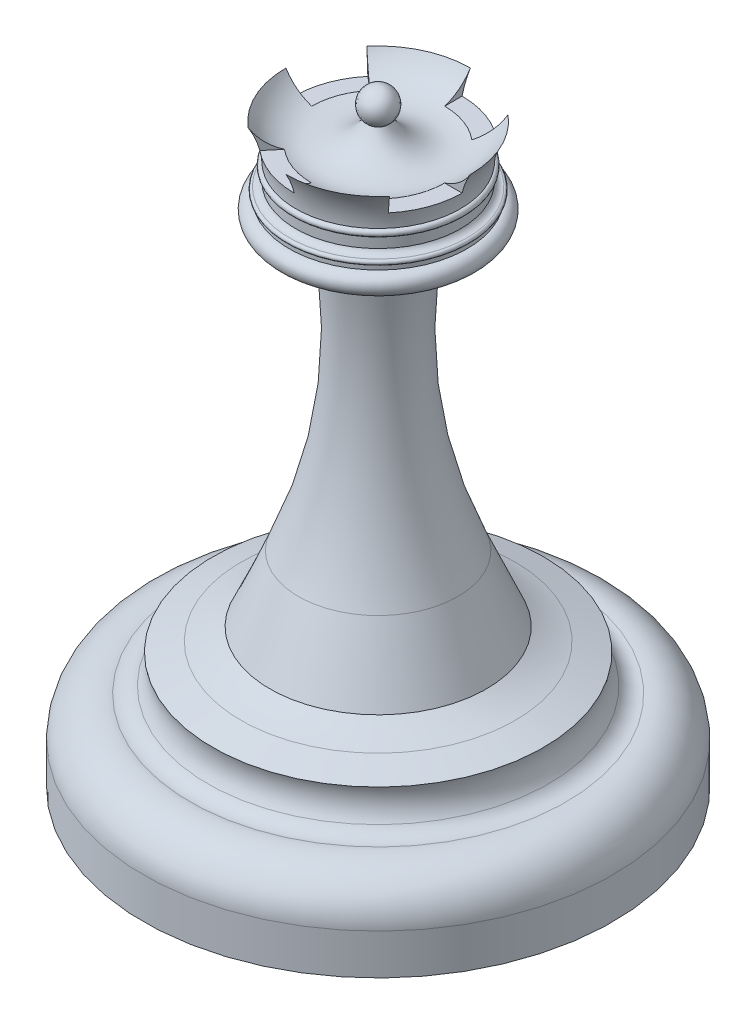
SolidWorks part; units mm, degrees
material "PVC Rigid"
ref_plane "Front Plane" through (0, 0, 0) normal (0, 0, 1) x (1, 0, 0)
ref_plane "Top Plane" through (0, 0, 0) normal (0, 1, 0) x (1, 0, 0)
ref_plane "Right Plane" through (0, 0, 0) normal (1, 0, 0) x (0, 0, -1)
sketch "Sketch1" plane through (0, 0, 0) normal (0, 0, 1) x (1, 0, 0)
  line L0 (0, 0) -> (-11.6, 0)
  line L3 (-11.5941, 2) -> (-11.6, 0)
  line L11 (0, 0) -> (0, 36.8797) construction
  line L18 (-8.1731, 5.7487) -> (-6.7792, 6.2131)
  line L19 (-5.3519, 6.8465) -> (-3.9421, 10.0987)
  line L20 (-2.4418, 24.2158) -> (-4.3963, 24.2158)
  line L21 (-4.3963, 25.21) -> (-4.3963, 25.4429)
  line L22 (-4.0678, 25.8995) -> (-4.0678, 26.4287)
  line L23 (0, 30) -> (0, 0)
  arc A0 (-9.2853, 3.9701) -> (-11.5941, 2) centre (-9.5941, 1.9941) ccw
  arc A11 (-9.2853, 3.9701) -> (-8.4185, 4.314) centre (-9.1435, 4.8771) ccw
  arc A12 (-8.4185, 4.314) -> (-8.1731, 5.7487) centre (-9.6376, 5.2608) ccw
  arc A13 (-6.7792, 6.2131) -> (-5.3519, 6.8465) centre (-9.3521, 13.936) ccw
  arc A14 (-3.9421, 10.0987) -> (-2.4418, 24.2158) centre (-25.757, 19.5554) ccw
  arc A15 (-4.3963, 24.2158) -> (-4.3963, 25.21) centre (-4.3963, 24.7129) cw
  arc A16 (-4.3963, 25.4429) -> (-4.3963, 25.6804) centre (-4.3963, 25.5616) cw
  arc A17 (-4.3963, 25.6804) -> (-4.0678, 25.8995) centre (-4.3963, 26.036) ccw
  arc A18 (-4.0678, 26.4287) -> (-4.0678, 26.7561) centre (-4.0678, 26.5924) cw
  circle A21 centre (0, 29.1999) radius 0.8001 construction
  arc A22 (-0.4915, 28.5685) -> (0, 30) centre (0.0013, 29.1994) cw
  arc A23 (-4.0678, 26.7561) -> (-4.5584, 28.4734) centre (-7.3469, 26.7481) ccw
  arc A25 (-4.5584, 28.4734) -> (-0.4915, 28.5685) centre (-2.5529, 29.7142) ccw
  dimension "D6" = 0.1637
  dimension "D4" = 3.2791
  dimension "D3" = 0.8006
  dimension "D8" = 0.3557
  dimension "D9" = 0.1187
  dimension "D11" = 0.4971
  dimension "D13" = 8.1402
  dimension "D15" = 1.5436
  dimension "D16" = 0.918
  dimension "D17" = 2
  dimension "D19" = 3.9701
  dimension "D23" = 2.3584
  dimension "D1" = 2
  dimension "D5" = 11.6
  dimension "D7" = 0.5292
  dimension "D10" = 0.233
  dimension "D12" = 1.9545
  dimension "D14" = 1.4693
  dimension "D18" = 30
  dimension "D20" = 8.1731
  dimension "D22" = 5.7487
  dimension "D24" = 4.5584
  dimension "D25" = 0.4915
  dimension "D26" = 28.4734
revolve "Revolve6" add sketch "Sketch1" angle 360 about L11 region at (-3.4178, 9.9826, 0)
sketch "Sketch4" plane through (0, 0, 0) normal (0, 0, 1) x (1, 0, 0)
  line L0 (-4.5584, 29.3797) -> (-4.5584, 28.4734)
  line L1 (-6.5739, 29.3797) -> (-2.543, 29.3797)
  line L2 (-6.5739, 29.3797) -> (-6.5739, 27.4734)
  line L3 (-6.5739, 27.4734) -> (-2.543, 27.4734)
  line L4 (-2.543, 29.3797) -> (-2.543, 27.4734)
  point P4 (-4.5584, 29.3797)
  dimension "D1" = 1
  dimension "D2" = 1.9063
revolve "Cut-Revolve2" cut sketch "Sketch4" angle 40 about L11 region at (-4.5584, 28.4265, 0) reverse direction yes
sketch "Sketch5" plane through (0, 0, 0) normal (0, 0, 1) x (1, 0, 0)
  line L0 (4.5584, 28.4734) -> (-4.5584, 28.4734) construction
  line L1 (2.676, 29.1349) -> (6.4408, 29.1349)
  line L2 (2.676, 29.1349) -> (2.676, 27.4734)
  line L3 (2.676, 27.4734) -> (6.4408, 27.4734)
  line L4 (6.4408, 29.1349) -> (6.4408, 27.4734)
  line L5 (4.5584, 28.4734) -> (4.5584, 29.1349) construction
  point P6 (4.5584, 29.1349)
  point P7 (4.5584, 28.4734)
  dimension "D1" = 1
revolve "Cut-Revolve3" cut sketch "Sketch5" angle 40 about L11 reverse direction yes
sketch "Sketch6" plane through (0, 0, 0) normal (1, 0, 0) x (0, 0, -1)
  line L0 (4.5584, 28.4734) -> (0, 28.4734) construction
  line L1 (3.0767, 28.9412) -> (6.0401, 28.9412)
  line L2 (3.0767, 28.9412) -> (3.0767, 27.4734)
  line L3 (3.0767, 27.4734) -> (6.0401, 27.4734)
  line L4 (6.0401, 28.9412) -> (6.0401, 27.4734)
  line L5 (4.5584, 28.4734) -> (4.5584, 28.9412) construction
  point P6 (4.5584, 28.9412)
  point P7 (4.5584, 28.4734)
  dimension "D1" = 1
revolve "Cut-Revolve4" cut sketch "Sketch6" angle 40 about L11 reverse direction yes
sketch "Sketch7" plane through (0, 0, 0) normal (1, 0, 0) x (0, 0, -1)
  line L0 (-4.5584, 28.4734) -> (0, 28.4734) construction
  line L1 (-6.4952, 29.3291) -> (-2.5801, 29.3291)
  line L2 (-6.4952, 29.3291) -> (-6.4952, 27.4734)
  line L3 (-6.4952, 27.4734) -> (-2.5801, 27.4734)
  line L4 (-2.5801, 29.3291) -> (-2.5801, 27.4734)
  line L5 (-4.5377, 29.3291) -> (-4.5377, 28.4734) construction
  point P4 (-4.5377, 29.3291)
  point P5 (-4.5377, 28.4734)
  point P10 (-8.6791, 27.4334)
  dimension "D1" = 1
revolve "Cut-Revolve5" cut sketch "Sketch7" angle 40 about L11 reverse direction yes
sketch "Sketch8" plane through (0, 0, 0) normal (0, -1, 0) x (1, 0, 0)
  circle A0 centre (0, 0) radius 10
extrude "Cut-Extrude1" cut sketch "Sketch8" against normal blind 2 from offset 0.4 offset against normal yes
